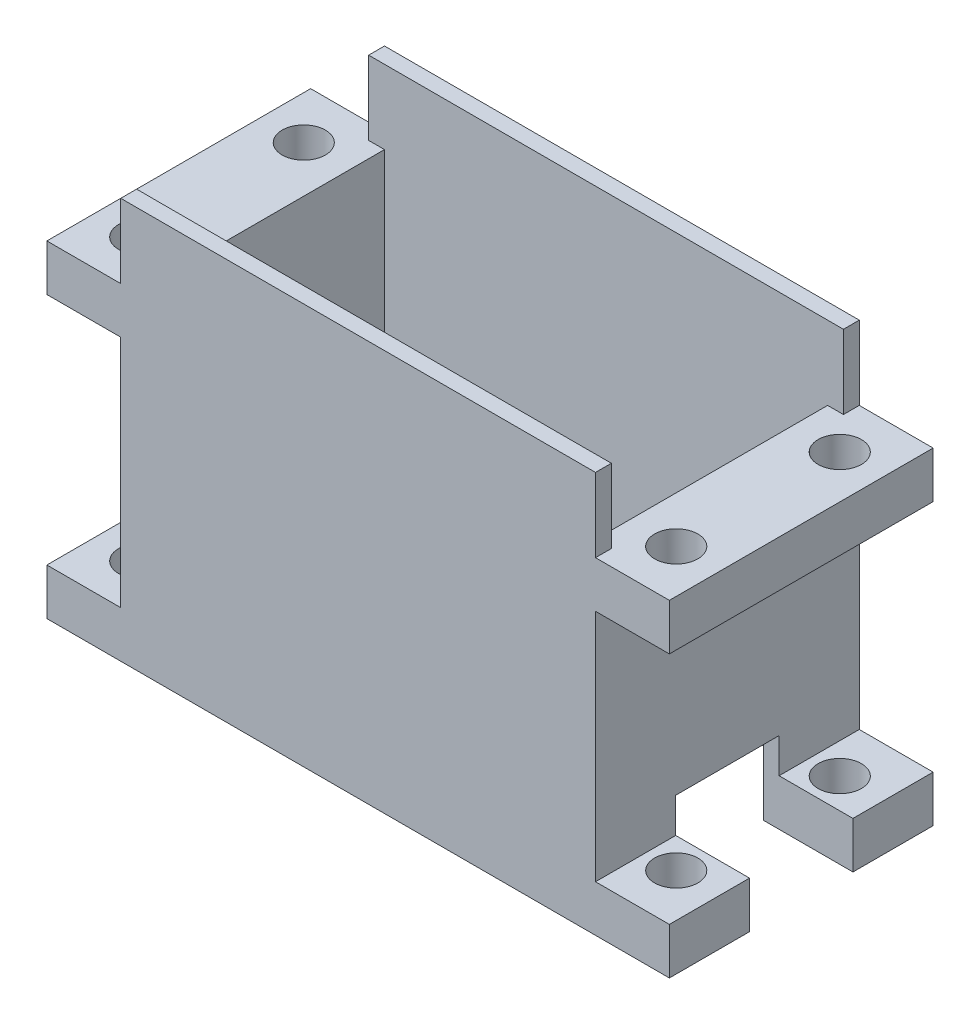
SolidWorks part; units mm, degrees
material "ABS"
ref_plane "Front Plane" through (0, 0, 0) normal (0, 0, 1) x (1, 0, 0)
ref_plane "Top Plane" through (0, 0, 0) normal (0, 1, 0) x (1, 0, 0)
ref_plane "Right Plane" through (0, 0, 0) normal (1, 0, 0) x (0, 0, -1)
sketch "Sketch1" plane through (0, 0, 0) normal (0, 1, 0) x (1, 0, 0)
  line L0 (-1.5, 23.5) -> (43.5, 23.5)
  line L1 (0, 0) -> (42, 0)
  line L2 (0, 0) -> (0, 22)
  line L3 (0, 22) -> (42, 22)
  line L4 (42, 0) -> (42, 22)
  line L5 (43.5, -1.5) -> (43.5, 23.5)
  line L6 (-1.5, -1.5) -> (43.5, -1.5)
  line L7 (-1.5, -1.5) -> (-1.5, 23.5)
  dimension "D1" = 22
  dimension "D2" = 42
  dimension "D3" = 1.5
extrude "Boss-Extrude1" add sketch "Sketch1" along normal blind 38
sketch "Sketch3" plane through (43.5, 0, 0) normal (1, 0, 0) x (0, 0, -1)
  line L0 (23.5, 38) -> (23.5, 33.9)
  line L2 (-1.5, 38) -> (23.5, 38) construction
  line L7 (22, 38) -> (0.0048, 38)
  line L8 (0.0048, 38) -> (0.0048, 31)
  line L9 (22, 31) -> (0.0048, 31)
  line L10 (22, 38) -> (22, 31)
  line L11 (-1.5, 38) -> (-1.5, 0) construction
  point P2 (-3.4456, 29.4)
  dimension "D1" = 7
  dimension "4.6" = 4.1
  dimension "D2" = 1.5
  dimension "D3" = 1.5048
  dimension "D4" = 21.9952
extrude "Cut-Extrude2" cut sketch "Sketch3" against normal through all both and the other way through all contours L10 L7 L8 L9 region at (43.5, 34.5, -11.0024)
sketch "Sketch4" plane through (43.5, 0, 0) normal (1, 0, 0) x (0, 0, -1)
  line L0 (-1.5, 31) -> (23.5, 31)
  line L1 (-1.5, 38) -> (-1.5, 0) construction
  line L2 (23.5, 38) -> (23.5, 0) construction
  line L3 (23.5, 31) -> (23.5, 26.6)
  line L4 (23.5, 26.6) -> (-1.5, 26.6)
  line L5 (-1.5, 26.6) -> (-1.5, 31)
  line L6 (-1.5, 0) -> (23.5, 0) construction
  dimension "D2" = 26.6
extrude "Boss-Extrude3" add sketch "Sketch4" along normal blind 7
sketch "Sketch8" plane through (0, 31, 0) normal (0, 1, 0) x (1, 0, 0)
  line L0 (50.5, 23.5) -> (43.5, 23.5) construction
  line L1 (42, 0.0048) -> (42, 22) construction
  line L2 (-1.5, 11.0024) -> (50.5, 11) construction
  line L3 (-1.5, 22) -> (-1.5, 0.0048) construction
  line L4 (50.5, 23.5) -> (50.5, -1.5) construction
  circle A0 centre (46.4, 18.75) radius 2.05
  circle A1 centre (46.3993, 3.2504) radius 2.05
  dimension "D3" = 4.1
  dimension "D1" = 4.75
  dimension "D2" = 4.4
extrude "Cut-Extrude5" cut sketch "Sketch8" against normal up to surface (4.4 mm away) up to face at (47, 26.6, -11)
ref_plane "Plane1" through (21, 0, 0) normal (1, 0, 0) x (0, 0, -1)
mirror "Mirror1" about plane through (21, 0, 0) normal (1, 0, 0) of "Cut-Extrude5", "Cut-Extrude2", "Boss-Extrude3"
sketch "Sketch6" plane through (43.5, 0, 0) normal (1, 0, 0) x (0, 0, -1)
  line L0 (15.9, -3.0571) -> (6.1, -3.0571)
  line L1 (22, 31) -> (22, 0) construction
  line L4 (6.1, 7.7) -> (6.1, -3.0571)
  line L5 (15.9, 7.7) -> (6.1, 7.7)
  line L10 (15.9, 7.7) -> (15.9, -3.0571)
  line L11 (-1.5, 0) -> (23.5, 0) construction
  line L13 (0, 38) -> (0, 0) construction
  point P15 (0, 0)
  dimension "D1" = 7.7
  dimension "D2" = 6.1
  dimension "D3" = 6.1
extrude "Cut-Extrude4" cut sketch "Sketch6" against normal blind 7 and the other way through all
ref_plane "Plane2" through (0, 15.5, 0) normal (0, 1, 0) x (1, 0, 0)
mirror "Mirror2" about plane through (0, 15.5, 0) normal (0, 1, 0) of "Mirror1", "Cut-Extrude2", "Boss-Extrude3", "Cut-Extrude5"
extrude "Cut-Extrude6" cut sketch "Sketch6<2>" along normal blind 15
sketch "Sketch6<2>" plane through (43.5, 0, 0) normal (1, 0, 0) x (0, 0, -1) same geometry as "Sketch6"
